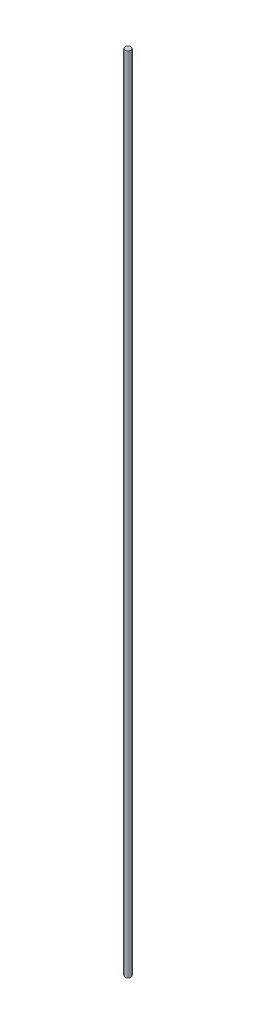
SolidWorks part; units mm, degrees
ref_plane "Спереди" through (0, 0, 0) normal (0, 0, 1) x (1, 0, 0)
ref_plane "Сверху" through (0, 0, 0) normal (0, 1, 0) x (1, 0, 0)
ref_plane "Справа" through (0, 0, 0) normal (1, 0, 0) x (0, 0, -1)
sketch "Эскиз1" plane through (0, 0, 0) normal (0, 1, 0) x (1, 0, 0)
  circle A0 centre (0, 0) radius 15
  dimension "D1" = 30
extrude "Бобышка-Вытянуть1" add sketch "Эскиз1" along normal blind 4000
ref_axis "Ось1" through (0, 4000, 0) along (0, -1, 0)
